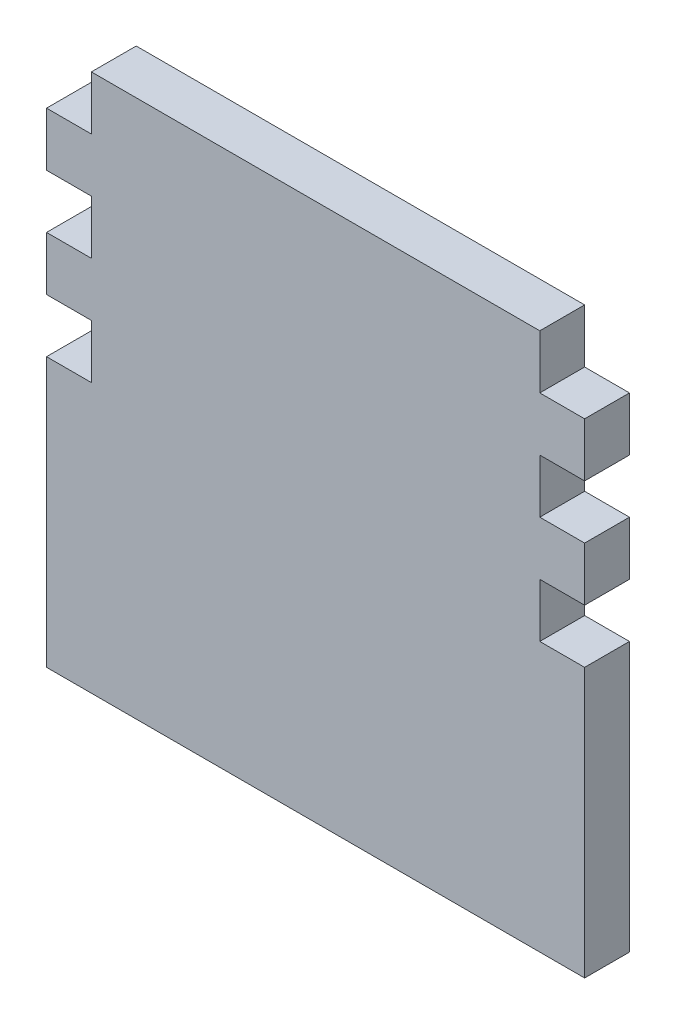
SolidWorks part; units mm, degrees
ref_plane "Front Plane" through (0, 0, 0) normal (0, 0, 1) x (1, 0, 0)
ref_plane "Top Plane" through (0, 0, 0) normal (0, 1, 0) x (1, 0, 0)
ref_plane "Right Plane" through (0, 0, 0) normal (1, 0, 0) x (0, 0, -1)
sketch "Sketch1" plane through (0, 0, 0) normal (0, 0, 1) x (1, 0, 0)
  line L1 (-37.8801, 17.0433) -> (38.3199, 17.0433)
  line L2 (-37.8801, 17.0433) -> (-37.8801, -59.1567)
  line L3 (-37.8801, -59.1567) -> (38.3199, -59.1567)
  line L4 (38.3199, 17.0433) -> (38.3199, -59.1567)
  dimension "D1" = 76.2
  dimension "D2" = 76.2
extrude "Boss-Extrude1" add sketch "Sketch1" along normal blind 6.35
sketch "Sketch2" plane through (0, 0, 6.35) normal (0, 0, 1) x (1, 0, 0)
  line L0 (-37.8801, 17.0433) -> (-31.5301, 17.0433)
  line L1 (38.3199, 17.0433) -> (-37.8801, 17.0433) construction
  line L2 (-31.5301, 17.0433) -> (-31.5301, 9.4233)
  line L3 (-31.5301, 9.4233) -> (-37.8801, 9.4233)
  line L4 (-37.8801, 17.0433) -> (-37.8801, -59.1567) construction
  line L5 (-37.8801, 9.4233) -> (-37.8801, 1.8033)
  line L6 (-37.8801, 1.8033) -> (-31.5301, 1.8033)
  line L7 (-31.5301, 1.8033) -> (-31.5301, -5.8167)
  line L8 (-31.5301, -5.8167) -> (-37.8801, -5.8167)
  line L9 (-37.8801, -5.8167) -> (-37.8801, -13.4367)
  line L10 (-37.8801, -13.4367) -> (-31.5301, -13.4367)
  line L11 (-31.5301, -13.4367) -> (-31.5301, -21.0567)
  line L12 (-31.5301, -21.0567) -> (-37.8801, -21.0567)
  line L13 (-37.8801, -21.0567) -> (-46.7258, -21.0567)
  line L14 (-37.8801, -21.0567) -> (-37.8801, -28.6767) [skipped]
  line L15 (-46.7258, -21.0567) -> (-46.7258, 17.0433)
  line L16 (-46.7258, 17.0433) -> (-37.8801, 17.0433)
  line L19 (47.1657, -21.0567) -> (47.1657, 17.0433)
  line L20 (38.3199, -21.0567) -> (47.1657, -21.0567)
  line L21 (31.9699, -21.0567) -> (38.3199, -21.0567)
  line L22 (31.9699, -13.4367) -> (31.9699, -21.0567)
  line L23 (38.3199, -13.4367) -> (31.9699, -13.4367)
  line L24 (38.3199, -5.8167) -> (38.3199, -13.4367)
  line L25 (31.9699, -5.8167) -> (38.3199, -5.8167)
  line L26 (31.9699, 1.8033) -> (31.9699, -5.8167)
  line L27 (38.3199, 1.8033) -> (31.9699, 1.8033)
  line L28 (38.3199, 9.4233) -> (38.3199, 1.8033)
  line L29 (31.9699, 9.4233) -> (38.3199, 9.4233)
  line L30 (31.9699, 17.0433) -> (31.9699, 9.4233)
  line L31 (38.3199, 17.0433) -> (31.9699, 17.0433)
  line L32 (47.1657, 17.0433) -> (38.3199, 17.0433)
  dimension "D1" = 7.62
  dimension "D2" = 7.62
  dimension "D3" = 6.35
  dimension "D4" = 6.35
  dimension "D6" = 38.1
  dimension "D5" = 3
extrude "Cut-Extrude1" cut sketch "Sketch2" against normal blind 6.35
